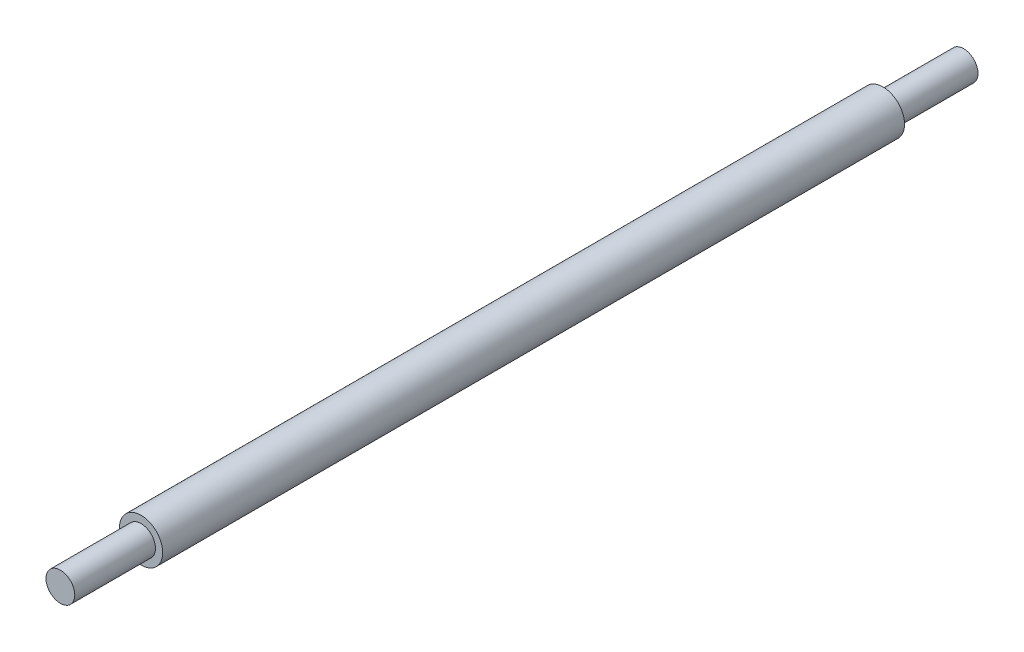
SolidWorks part; units mm, degrees
material "6061 Alloy"
ref_plane "Front" through (0, 0, 0) normal (0, 0, 1) x (1, 0, 0)
ref_plane "Top" through (0, 0, 0) normal (0, 1, 0) x (1, 0, 0)
ref_plane "Right" through (0, 0, 0) normal (1, 0, 0) x (0, 0, -1)
sketch "Sketch1" plane through (0, 0, 0) normal (0, 0, 1) x (1, 0, 0)
  circle A0 centre (0, 0) radius 9.525
  dimension "D1" = 19.05
extrude "Boss-Extrude1" add sketch "Sketch1" along normal blind 327.025
sketch "Sketch2" plane through (0, 0, 327.025) normal (0, 0, 1) x (1, 0, 0)
  circle A0 centre (0, 0) radius 6.35
  dimension "D1" = 12.7
extrude "Boss-Extrude2" add sketch "Sketch2" along normal blind 35.56
sketch "Sketch3" plane through (0, 0, 0) normal (0, 0, -1) x (-1, 0, 0)
  circle A0 centre (0, 0) radius 6.35
  dimension "D1" = 12.7
extrude "Boss-Extrude3" add sketch "Sketch3" along normal blind 35.56
